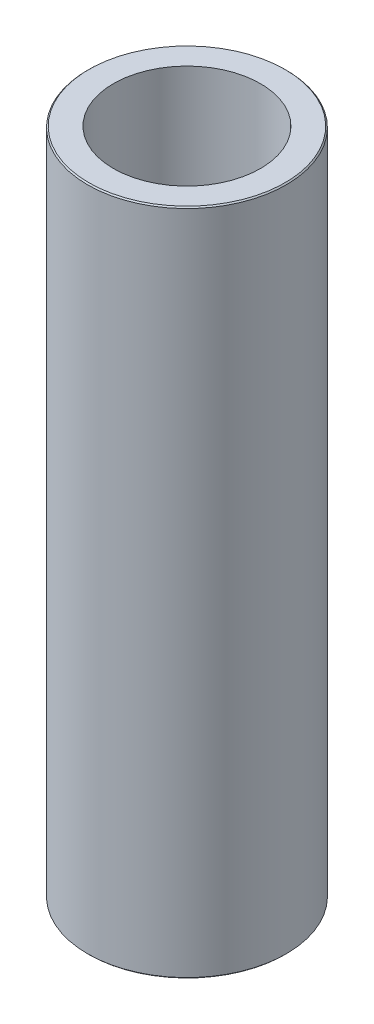
SolidWorks part; units mm, degrees
ref_plane "Front Plane" through (0, 0, 0) normal (0, 0, 1) x (1, 0, 0)
ref_plane "Top Plane" through (0, 0, 0) normal (0, 1, 0) x (1, 0, 0)
ref_plane "Right Plane" through (0, 0, 0) normal (1, 0, 0) x (0, 0, -1)
sketch "Sketch1" plane through (0, 0, 0) normal (0, 1, 0) x (1, 0, 0)
  circle A0 centre (0, 0) radius 25
  dimension "SHAFT_OD" = 50
extrude "Boss-Extrude1" add sketch "Sketch1" along normal blind 168.2356
sketch "Sketch2" plane through (0, 0, 0) normal (0, 1, 0) x (1, 0, 0)
  circle A0 centre (0, 0) radius 18.5136
  dimension "BORE_D" = 37.0271
extrude "Cut-Extrude1" cut sketch "Sketch2" along normal through all
chamfer "Chamfer1" distance 0.3048 angle 45 2 edges at (0, 168.2356, 25) (0, 0, 25)
